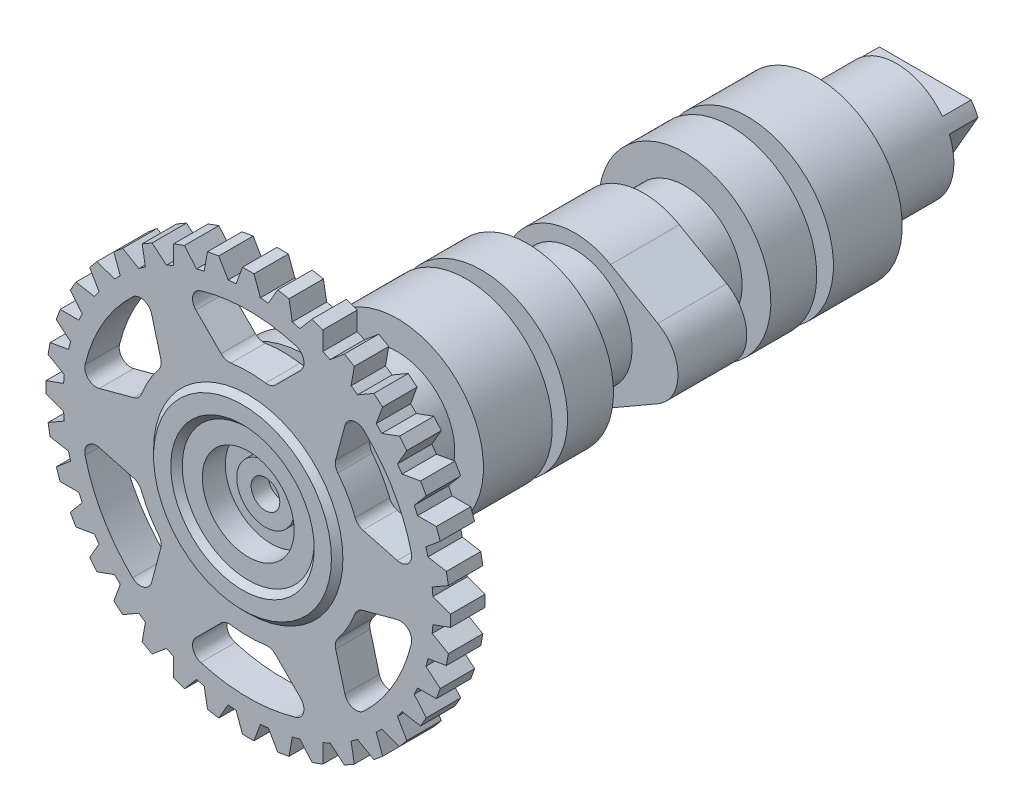
SolidWorks part; units mm, degrees
material "6061-T4 (SS)"
ref_plane "Front Plane" through (0, 0, 0) normal (0, 0, 1) x (1, 0, 0)
ref_plane "Top Plane" through (0, 0, 0) normal (0, 1, 0) x (1, 0, 0)
ref_plane "Right Plane" through (0, 0, 0) normal (1, 0, 0) x (0, 0, -1)
sketch "Sketch1" plane through (0, 0, 0) normal (0, 0, 1) x (1, 0, 0)
  circle A0 centre (0, 0) radius 10
  dimension "D1" = 20
extrude "Shaft" add sketch "Sketch1" along normal blind 118
sketch "Sketch2" plane through (0, 0, 118) normal (0, 0, 1) x (1, 0, 0)
  line L0 (0, 29.25) -> (0, 0) construction
  line L1 (-4.7374, 20.3333) -> (-9.1259, 24.7218)
  line L2 (4.7374, 20.3333) -> (9.1259, 24.7218)
  line L3 (15.2405, 14.2694) -> (16.8468, 20.2642)
  line L4 (19.9779, 6.0639) -> (25.9727, 4.4576)
  line L5 (19.9779, -6.0639) -> (25.9727, -4.4576)
  line L6 (15.2405, -14.2694) -> (16.8468, -20.2642)
  line L7 (4.7374, -20.3333) -> (9.1259, -24.7218)
  line L8 (-4.7374, -20.3333) -> (-9.1259, -24.7218)
  line L9 (-15.2405, -14.2694) -> (-16.8468, -20.2642)
  line L10 (-19.9779, -6.0639) -> (-25.9727, -4.4576)
  line L11 (-19.9779, 6.0639) -> (-25.9727, 4.4576)
  line L12 (-15.2405, 14.2694) -> (-16.8468, 20.2642)
  circle A0 centre (0, 0) radius 35.25 construction
  arc A1 (8.2777, 28.0543) -> (-8.2777, 28.0543) centre (0, 0) ccw
  circle A2 centre (0, 0) radius 32.25 construction
  circle A3 centre (0, 0) radius 29.25 construction
  circle A4 centre (0, 0) radius 20
  arc A5 (3.0211, 19.7705) -> (-3.0211, 19.7705) centre (0, 0) ccw
  arc A6 (-4.7374, 20.3333) -> (-3.0211, 19.7705) centre (-3.3232, 21.7476) ccw
  arc A7 (4.7374, 20.3333) -> (3.0211, 19.7705) centre (3.3232, 21.7476) cw
  arc A8 (9.1259, 24.7218) -> (8.2777, 28.0543) centre (7.7117, 26.136) ccw
  arc A9 (-9.1259, 24.7218) -> (-8.2777, 28.0543) centre (-7.7117, 26.136) cw
  arc A10 (18.6323, 7.2689) -> (15.6112, 12.5016) centre (0, 0) ccw
  arc A11 (19.9779, 6.0639) -> (18.6323, 7.2689) centre (20.4955, 7.9958) cw
  arc A12 (15.2405, 14.2694) -> (15.6112, 12.5016) centre (17.1723, 13.7518) ccw
  arc A13 (16.8468, 20.2642) -> (20.1569, 21.1958) centre (18.7786, 19.7465) cw
  arc A14 (28.4346, 6.8585) -> (20.1569, 21.1958) centre (0, 0) ccw
  arc A15 (25.9727, 4.4576) -> (28.4346, 6.8585) centre (26.4903, 6.3895) ccw
  arc A16 (15.6112, -12.5016) -> (18.6323, -7.2689) centre (0, 0) ccw
  arc A17 (15.2405, -14.2694) -> (15.6112, -12.5016) centre (17.1723, -13.7518) cw
  arc A18 (19.9779, -6.0639) -> (18.6323, -7.2689) centre (20.4955, -7.9958) ccw
  arc A19 (25.9727, -4.4576) -> (28.4346, -6.8585) centre (26.4903, -6.3895) cw
  arc A20 (20.1569, -21.1958) -> (28.4346, -6.8585) centre (0, 0) ccw
  arc A21 (16.8468, -20.2642) -> (20.1569, -21.1958) centre (18.7786, -19.7465) ccw
  arc A22 (-3.0211, -19.7705) -> (3.0211, -19.7705) centre (0, 0) ccw
  arc A23 (-4.7374, -20.3333) -> (-3.0211, -19.7705) centre (-3.3232, -21.7476) cw
  arc A24 (4.7374, -20.3333) -> (3.0211, -19.7705) centre (3.3232, -21.7476) ccw
  arc A25 (9.1259, -24.7218) -> (8.2777, -28.0543) centre (7.7117, -26.136) cw
  arc A26 (-8.2777, -28.0543) -> (8.2777, -28.0543) centre (0, 0) ccw
  arc A27 (-9.1259, -24.7218) -> (-8.2777, -28.0543) centre (-7.7117, -26.136) ccw
  arc A28 (-18.6323, -7.2689) -> (-15.6112, -12.5016) centre (0, 0) ccw
  arc A29 (-19.9779, -6.0639) -> (-18.6323, -7.2689) centre (-20.4955, -7.9958) cw
  arc A30 (-15.2405, -14.2694) -> (-15.6112, -12.5016) centre (-17.1723, -13.7518) ccw
  arc A31 (-16.8468, -20.2642) -> (-20.1569, -21.1958) centre (-18.7786, -19.7465) cw
  arc A32 (-28.4346, -6.8585) -> (-20.1569, -21.1958) centre (0, 0) ccw
  arc A33 (-25.9727, -4.4576) -> (-28.4346, -6.8585) centre (-26.4903, -6.3895) ccw
  arc A34 (-15.6112, 12.5016) -> (-18.6323, 7.2689) centre (0, 0) ccw
  arc A35 (-15.2405, 14.2694) -> (-15.6112, 12.5016) centre (-17.1723, 13.7518) cw
  arc A36 (-19.9779, 6.0639) -> (-18.6323, 7.2689) centre (-20.4955, 7.9958) ccw
  arc A37 (-25.9727, 4.4576) -> (-28.4346, 6.8585) centre (-26.4903, 6.3895) cw
  arc A38 (-20.1569, 21.1958) -> (-28.4346, 6.8585) centre (0, 0) ccw
  arc A39 (-16.8468, 20.2642) -> (-20.1569, 21.1958) centre (-18.7786, 19.7465) ccw
  circle A40 centre (0, 0) radius 32.25
  point P15 (-4, 19.5959)
  point P83 (0, 0)
  dimension "D1" = 70.5
  dimension "D5" = 2
  dimension "D4" = 4
  dimension "D2" = 6
  dimension "D3" = 10
  dimension "D7" = 3
  dimension "D6" = 6
extrude "Gear" add sketch "Sketch2" against normal blind 6
sketch "Sketch3" plane through (0, 0, 118) normal (0, 0, 1) x (1, 0, 0)
  line L0 (-2.1172, 32.1804) -> (-1, 35.25)
  line L1 (-1, 35.25) -> (1, 35.25)
  line L2 (1, 35.25) -> (2.1172, 32.1804)
  line L5 (0, 29.25) -> (0, 39.4669) construction
  line L6 (7.1059, 34.5408) -> (7.6731, 31.3239)
  line L7 (5.1363, 34.8881) -> (7.1059, 34.5408)
  line L8 (3.503, 32.0592) -> (5.1363, 34.8881)
  line L9 (12.9959, 32.7821) -> (12.9959, 29.5156)
  line L10 (11.1165, 33.4662) -> (12.9959, 32.7821)
  line L11 (9.0168, 30.9638) -> (11.1165, 33.4662)
  line L12 (18.491, 30.0274) -> (17.9238, 26.8104)
  line L13 (16.759, 31.0274) -> (18.491, 30.0274)
  line L14 (14.2566, 28.9277) -> (16.759, 31.0274)
  line L15 (23.4243, 26.3603) -> (22.3071, 23.2907)
  line L16 (21.8922, 27.6459) -> (23.4243, 26.3603)
  line L17 (19.0633, 26.0126) -> (21.8922, 27.6459)
  line L18 (27.6459, 21.8922) -> (26.0126, 19.0633)
  line L19 (26.3603, 23.4243) -> (27.6459, 21.8922)
  line L20 (23.2907, 22.3071) -> (26.3603, 23.4243)
  line L21 (31.0274, 16.759) -> (28.9277, 14.2566)
  line L22 (30.0274, 18.491) -> (31.0274, 16.759)
  line L23 (26.8104, 17.9238) -> (30.0274, 18.491)
  line L24 (33.4662, 11.1165) -> (30.9638, 9.0168)
  line L25 (32.7821, 12.9959) -> (33.4662, 11.1165)
  line L26 (29.5156, 12.9959) -> (32.7821, 12.9959)
  line L27 (34.8881, 5.1363) -> (32.0592, 3.503)
  line L28 (34.5408, 7.1059) -> (34.8881, 5.1363)
  line L29 (31.3239, 7.6731) -> (34.5408, 7.1059)
  line L30 (35.25, -1) -> (32.1804, -2.1172)
  line L31 (35.25, 1) -> (35.25, -1)
  line L32 (32.1804, 2.1172) -> (35.25, 1)
  line L33 (34.5408, -7.1059) -> (31.3239, -7.6731)
  line L34 (34.8881, -5.1363) -> (34.5408, -7.1059)
  line L35 (32.0592, -3.503) -> (34.8881, -5.1363)
  line L36 (32.7821, -12.9959) -> (29.5156, -12.9959)
  line L37 (33.4662, -11.1165) -> (32.7821, -12.9959)
  line L38 (30.9638, -9.0168) -> (33.4662, -11.1165)
  line L39 (30.0274, -18.491) -> (26.8104, -17.9238)
  line L40 (31.0274, -16.759) -> (30.0274, -18.491)
  line L41 (28.9277, -14.2566) -> (31.0274, -16.759)
  line L42 (26.3603, -23.4243) -> (23.2907, -22.3071)
  line L43 (27.6459, -21.8922) -> (26.3603, -23.4243)
  line L44 (26.0126, -19.0633) -> (27.6459, -21.8922)
  line L45 (21.8922, -27.6459) -> (19.0633, -26.0126)
  line L46 (23.4243, -26.3603) -> (21.8922, -27.6459)
  line L47 (22.3071, -23.2907) -> (23.4243, -26.3603)
  line L48 (16.759, -31.0274) -> (14.2566, -28.9277)
  line L49 (18.491, -30.0274) -> (16.759, -31.0274)
  line L50 (17.9238, -26.8104) -> (18.491, -30.0274)
  line L51 (11.1165, -33.4662) -> (9.0168, -30.9638)
  line L52 (12.9959, -32.7821) -> (11.1165, -33.4662)
  line L53 (12.9959, -29.5156) -> (12.9959, -32.7821)
  line L54 (5.1363, -34.8881) -> (3.503, -32.0592)
  line L55 (7.1059, -34.5408) -> (5.1363, -34.8881)
  line L56 (7.6731, -31.3239) -> (7.1059, -34.5408)
  line L57 (-1, -35.25) -> (-2.1172, -32.1804)
  line L58 (1, -35.25) -> (-1, -35.25)
  line L59 (2.1172, -32.1804) -> (1, -35.25)
  line L60 (-7.1059, -34.5408) -> (-7.6731, -31.3239)
  line L61 (-5.1363, -34.8881) -> (-7.1059, -34.5408)
  line L62 (-3.503, -32.0592) -> (-5.1363, -34.8881)
  line L63 (-12.9959, -32.7821) -> (-12.9959, -29.5156)
  line L64 (-11.1165, -33.4662) -> (-12.9959, -32.7821)
  line L65 (-9.0168, -30.9638) -> (-11.1165, -33.4662)
  line L66 (-18.491, -30.0274) -> (-17.9238, -26.8104)
  line L67 (-16.759, -31.0274) -> (-18.491, -30.0274)
  line L68 (-14.2566, -28.9277) -> (-16.759, -31.0274)
  line L69 (-23.4243, -26.3603) -> (-22.3071, -23.2907)
  line L70 (-21.8922, -27.6459) -> (-23.4243, -26.3603)
  line L71 (-19.0633, -26.0126) -> (-21.8922, -27.6459)
  line L72 (-27.6459, -21.8922) -> (-26.0126, -19.0633)
  line L73 (-26.3603, -23.4243) -> (-27.6459, -21.8922)
  line L74 (-23.2907, -22.3071) -> (-26.3603, -23.4243)
  line L75 (-31.0274, -16.759) -> (-28.9277, -14.2566)
  line L76 (-30.0274, -18.491) -> (-31.0274, -16.759)
  line L77 (-26.8104, -17.9238) -> (-30.0274, -18.491)
  line L78 (-33.4662, -11.1165) -> (-30.9638, -9.0168)
  line L79 (-32.7821, -12.9959) -> (-33.4662, -11.1165)
  line L80 (-29.5156, -12.9959) -> (-32.7821, -12.9959)
  line L81 (-34.8881, -5.1363) -> (-32.0592, -3.503)
  line L82 (-34.5408, -7.1059) -> (-34.8881, -5.1363)
  line L83 (-31.3239, -7.6731) -> (-34.5408, -7.1059)
  line L84 (-35.25, 1) -> (-32.1804, 2.1172)
  line L85 (-35.25, -1) -> (-35.25, 1)
  line L86 (-32.1804, -2.1172) -> (-35.25, -1)
  line L87 (-34.5408, 7.1059) -> (-31.3239, 7.6731)
  line L88 (-34.8881, 5.1363) -> (-34.5408, 7.1059)
  line L89 (-32.0592, 3.503) -> (-34.8881, 5.1363)
  line L90 (-32.7821, 12.9959) -> (-29.5156, 12.9959)
  line L91 (-33.4662, 11.1165) -> (-32.7821, 12.9959)
  line L92 (-30.9638, 9.0168) -> (-33.4662, 11.1165)
  line L93 (-30.0274, 18.491) -> (-26.8104, 17.9238)
  line L94 (-31.0274, 16.759) -> (-30.0274, 18.491)
  line L95 (-28.9277, 14.2566) -> (-31.0274, 16.759)
  line L96 (-26.3603, 23.4243) -> (-23.2907, 22.3071)
  line L97 (-27.6459, 21.8922) -> (-26.3603, 23.4243)
  line L98 (-26.0126, 19.0633) -> (-27.6459, 21.8922)
  line L99 (-21.8922, 27.6459) -> (-19.0633, 26.0126)
  line L100 (-23.4243, 26.3603) -> (-21.8922, 27.6459)
  line L101 (-22.3071, 23.2907) -> (-23.4243, 26.3603)
  line L102 (-16.759, 31.0274) -> (-14.2566, 28.9277)
  line L103 (-18.491, 30.0274) -> (-16.759, 31.0274)
  line L104 (-17.9238, 26.8104) -> (-18.491, 30.0274)
  line L105 (-11.1165, 33.4662) -> (-9.0168, 30.9638)
  line L106 (-12.9959, 32.7821) -> (-11.1165, 33.4662)
  line L107 (-12.9959, 29.5156) -> (-12.9959, 32.7821)
  line L108 (-5.1363, 34.8881) -> (-3.503, 32.0592)
  line L109 (-7.1059, 34.5408) -> (-5.1363, 34.8881)
  line L110 (-7.6731, 31.3239) -> (-7.1059, 34.5408)
  circle A0 centre (0, 0) radius 32.25 construction
  circle A1 centre (0, 0) radius 32.25 construction
  circle A2 centre (0, 0) radius 35.25 construction
  arc A3 (-2.1172, 32.1804) -> (2.1172, 32.1804) centre (0, 0) cw
  arc A4 (3.503, 32.0592) -> (7.6731, 31.3239) centre (0, 0) cw
  arc A5 (9.0168, 30.9638) -> (12.9959, 29.5156) centre (0, 0) cw
  arc A6 (14.2566, 28.9277) -> (17.9238, 26.8104) centre (0, 0) cw
  arc A7 (19.0633, 26.0126) -> (22.3071, 23.2907) centre (0, 0) cw
  arc A8 (23.2907, 22.3071) -> (26.0126, 19.0633) centre (0, 0) cw
  arc A9 (26.8104, 17.9238) -> (28.9277, 14.2566) centre (0, 0) cw
  arc A10 (29.5156, 12.9959) -> (30.9638, 9.0168) centre (0, 0) cw
  arc A11 (31.3239, 7.6731) -> (32.0592, 3.503) centre (0, 0) cw
  arc A12 (32.1804, 2.1172) -> (32.1804, -2.1172) centre (0, 0) cw
  arc A13 (32.0592, -3.503) -> (31.3239, -7.6731) centre (0, 0) cw
  arc A14 (30.9638, -9.0168) -> (29.5156, -12.9959) centre (0, 0) cw
  arc A15 (28.9277, -14.2566) -> (26.8104, -17.9238) centre (0, 0) cw
  arc A16 (26.0126, -19.0633) -> (23.2907, -22.3071) centre (0, 0) cw
  arc A17 (22.3071, -23.2907) -> (19.0633, -26.0126) centre (0, 0) cw
  arc A18 (17.9238, -26.8104) -> (14.2566, -28.9277) centre (0, 0) cw
  arc A19 (12.9959, -29.5156) -> (9.0168, -30.9638) centre (0, 0) cw
  arc A20 (7.6731, -31.3239) -> (3.503, -32.0592) centre (0, 0) cw
  arc A21 (2.1172, -32.1804) -> (-2.1172, -32.1804) centre (0, 0) cw
  arc A22 (-3.503, -32.0592) -> (-7.6731, -31.3239) centre (0, 0) cw
  arc A23 (-9.0168, -30.9638) -> (-12.9959, -29.5156) centre (0, 0) cw
  arc A24 (-14.2566, -28.9277) -> (-17.9238, -26.8104) centre (0, 0) cw
  arc A25 (-19.0633, -26.0126) -> (-22.3071, -23.2907) centre (0, 0) cw
  arc A26 (-23.2907, -22.3071) -> (-26.0126, -19.0633) centre (0, 0) cw
  arc A27 (-26.8104, -17.9238) -> (-28.9277, -14.2566) centre (0, 0) cw
  arc A28 (-29.5156, -12.9959) -> (-30.9638, -9.0168) centre (0, 0) cw
  arc A29 (-31.3239, -7.6731) -> (-32.0592, -3.503) centre (0, 0) cw
  arc A30 (-32.1804, -2.1172) -> (-32.1804, 2.1172) centre (0, 0) cw
  arc A31 (-32.0592, 3.503) -> (-31.3239, 7.6731) centre (0, 0) cw
  arc A32 (-30.9638, 9.0168) -> (-29.5156, 12.9959) centre (0, 0) cw
  arc A33 (-28.9277, 14.2566) -> (-26.8104, 17.9238) centre (0, 0) cw
  arc A34 (-26.0126, 19.0633) -> (-23.2907, 22.3071) centre (0, 0) cw
  arc A35 (-22.3071, 23.2907) -> (-19.0633, 26.0126) centre (0, 0) cw
  arc A36 (-17.9238, 26.8104) -> (-14.2566, 28.9277) centre (0, 0) cw
  arc A37 (-12.9959, 29.5156) -> (-9.0168, 30.9638) centre (0, 0) cw
  arc A38 (-7.6731, 31.3239) -> (-3.503, 32.0592) centre (0, 0) cw
  point P253 (0, 0)
  dimension "D1" = 110
  dimension "D2" = 2
  dimension "D3" = 36
extrude "Boss-Extrude3" add sketch "Sketch3" against normal up to surface (6 mm away) up to face at (10, 0, 112)
sketch "Sketch4" plane through (0, 0, 112) normal (0, 0, -1) x (-1, 0, 0)
  circle A0 centre (0, 0) radius 14
  circle A1 centre (0, 0) radius 10 construction
  dimension "D1" = 4
extrude "Boss-Extrude4" add sketch "Sketch4" along normal blind 3
sketch "Sketch5" plane through (0, 0, 112) normal (0, 0, -1) x (-1, 0, 0)
  circle A0 centre (0, 0) radius 17.5
  dimension "D1" = 35
extrude "Boss-Extrude5" add sketch "Sketch5" along normal blind 4 from offset 4
sketch "Sketch6" plane through (0, 0, 0) normal (0, 0, -1) x (-1, 0, 0)
  line L4 (-1.1962, -9.9282) -> (-9.1962, 3.9282)
  line L5 (-8, 6) -> (8, 6)
  line L6 (9.1962, 3.9282) -> (1.1962, -9.9282)
  line L7 (-10.3923, 6) -> (-8, 6) construction
  line L8 (-9.1962, 3.9282) -> (-10.3923, 6) construction
  line L9 (8, 6) -> (10.3923, 6) construction
  line L10 (10.3923, 6) -> (9.1962, 3.9282) construction
  line L11 (1.1962, -9.9282) -> (0, -12) construction
  line L12 (0, -12) -> (-1.1962, -9.9282) construction
  arc A0 (10.3923, 6) -> (-10.3923, 6) centre (0, 0) ccw construction
  circle A1 centre (0, 0) radius 10 construction
  arc A2 (-9.1962, 3.9282) -> (-1.1962, -9.9282) centre (0, 0) ccw
  arc A3 (-10.3923, 6) -> (10.3923, 6) centre (0, 0) ccw construction
  circle A4 centre (0, 0) radius 12 construction
  arc A5 (-8, 6) -> (-9.1962, 3.9282) centre (0, 0) ccw construction
  circle A6 centre (0, 0) radius 10 construction
  arc A7 (9.1962, 3.9282) -> (8, 6) centre (0, 0) ccw construction
  arc A8 (8, 6) -> (-8, 6) centre (0, 0) ccw
  arc A9 (-1.1962, -9.9282) -> (1.1962, -9.9282) centre (0, 0) ccw construction
  arc A10 (1.1962, -9.9282) -> (9.1962, 3.9282) centre (0, 0) ccw
  dimension "D2" = 16
  dimension "D1" = 2
extrude "Cut-Extrude1" cut sketch "Sketch6" against normal blind 5 and the other way through all
sketch "Sketch7" plane through (0, 0, 118) normal (0, 0, 1) x (1, 0, 0)
  circle A0 centre (0, 0) radius 8
  dimension "D1" = 16
extrude "Cut-Extrude2" cut sketch "Sketch7" against normal blind 3
sketch "Sketch8" plane through (0, 0, 115) normal (0, 0, 1) x (1, 0, 0)
  circle A0 centre (0, 0) radius 8
  circle A1 centre (0, 0) radius 5
  circle A2 centre (0, 0) radius 8 construction
  dimension "D1" = 10
extrude "Cut-Extrude3" cut sketch "Sketch8" against normal blind 1
sketch "Sketch9" plane through (0, 0, 115) normal (0, 0, 1) x (1, 0, 0)
  circle A0 centre (0, 0) radius 2.5
  dimension "D1" = 5
extrude "Cut-Extrude4" cut sketch "Sketch9" against normal blind 3
sketch "Sketch10" plane through (0, 0, 118) normal (0, 0, 1) x (1, 0, 0)
  circle A0 centre (0, 0) radius 12.5
  circle A1 centre (0, 0) radius 15.5
  dimension "D1" = 3
  dimension "D2" = 25
extrude "Boss-Extrude6" add sketch "Sketch10" along normal blind 1
chamfer "Chamfer1" distance 1 angle 45 2 edges at (12.5, 0, 118) (15.5, 0, 118)
sketch "Sketch11" plane through (0, 0, 112) normal (0, 0, -1) x (-1, 0, 0)
  line L0 (-4.4909, -14.312) -> (5.9611, -17.5916)
  line L1 (16.2892, -8.9253) -> (14.8744, 1.9374)
  line L2 (0, 0) -> (8.3562, -9.9586) construction
  line L3 (-8, 6) -> (8, 6) construction
  line L4 (2.6797, -25.165) -> (13.8928, -15.7561) construction
  line L5 (5.9611, -17.5916) -> (16.2892, -8.9253) construction
  arc A0 (14.8744, 1.9374) -> (-4.4909, -14.312) centre (0, 0) ccw
  arc A1 (-4.4909, -14.312) -> (14.8744, 1.9374) centre (0, 0) ccw construction
  arc A2 (5.9611, -17.5916) -> (16.2892, -8.9253) centre (8.3562, -9.9586) ccw
  point P10 (6.4279, -7.6604)
  dimension "D2" = 15
  dimension "D3" = 21
  dimension "D4" = 8
  dimension "D5" = 50
  dimension "D1" = 25.2795
extrude "Boss-Extrude7" add sketch "Sketch11" along normal blind 8 from offset 34.662
sketch "Sketch12" plane through (0, 0, 112) normal (0, 0, -1) x (-1, 0, 0)
  line L2 (-4.4909, -14.312) -> (5.9611, -17.5916)
  line L3 (16.2892, -8.9253) -> (14.8744, 1.9374)
  line L4 (-4.4909, -14.312) -> (5.9611, -17.5916)
  line L5 (16.2892, -8.9253) -> (14.8744, 1.9374)
  arc A2 (14.8744, 1.9374) -> (-4.4909, -14.312) centre (0, 0) ccw
  arc A3 (5.9611, -17.5916) -> (16.2892, -8.9253) centre (8.3562, -9.9586) ccw
  arc A4 (14.8744, 1.9374) -> (-4.4909, -14.312) centre (0, 0) ccw
  arc A5 (5.9611, -17.5916) -> (16.2892, -8.9253) centre (8.3562, -9.9586) ccw
  dimension "D1" = 0
extrude "Boss-Extrude8" add sketch "Sketch12" along normal blind 8 from offset 70.0933
sketch "Sketch13" plane through (0, 0, 112) normal (0, 0, -1) x (-1, 0, 0)
  circle A0 centre (0, 0) radius 15
  dimension "D1" = 30
extrude "Boss-Extrude9" add sketch "Sketch13" along normal blind 12 from offset 20
sketch "Sketch14" plane through (0, 0, 112) normal (0, 0, -1) x (-1, 0, 0)
  circle A0 centre (0, 0) radius 15 construction
  circle A1 centre (0, 0) radius 15
extrude "Boss-Extrude10" add sketch "Sketch14" along normal blind 12 from offset 81
sketch "Sketch15" plane through (0, 0, 112) normal (0, 0, -1) x (-1, 0, 0)
  line L4 (-6.25, 10.8253) -> (-14.5, 6.0622)
  line L5 (-6.25, -10.8253) -> (-14.5, -6.0622)
  line L6 (38.775, 0) -> (-38.775, 0) construction
  arc A0 (-6.25, -10.8253) -> (-6.25, 10.8253) centre (0, 0) ccw
  circle A2 centre (0, 0) radius 12.5 construction
  arc A5 (-14.5, -6.0622) -> (-14.5, 6.0622) centre (-11, 0) cw
  point P6 (-3, 0)
  point P9 (-4.789, 0)
  point P13 (-18, 0)
  dimension "D1" = 30
  dimension "D3" = 12.5
  dimension "D4" = 12.1244
  dimension "D5" = 18
  dimension "D2" = 30
extrude "Boss-Extrude11" add sketch "Sketch15" along normal blind 12 from offset 50.9
ref_plane "Plane1" through (0, 0, 115) normal (0, 0, 1) x (1, 0, 0)
ref_plane "Plane2" through (0, 0, 73.338) normal (0, 0, -1) x (-1, 0, 0)
ref_plane "Plane3" through (0, 0, 86) normal (0, 0, 1) x (1, 0, 0)
ref_plane "Plane4" through (0, 0, 37.9067) normal (0, 0, -1) x (-1, 0, 0)
ref_plane "Plane5" through (0, 0, 55.1) normal (0, 0, 1) x (1, 0, 0)
ref_plane "Plane6" through (0, 0, 25) normal (0, 0, -1) x (-1, 0, 0)
